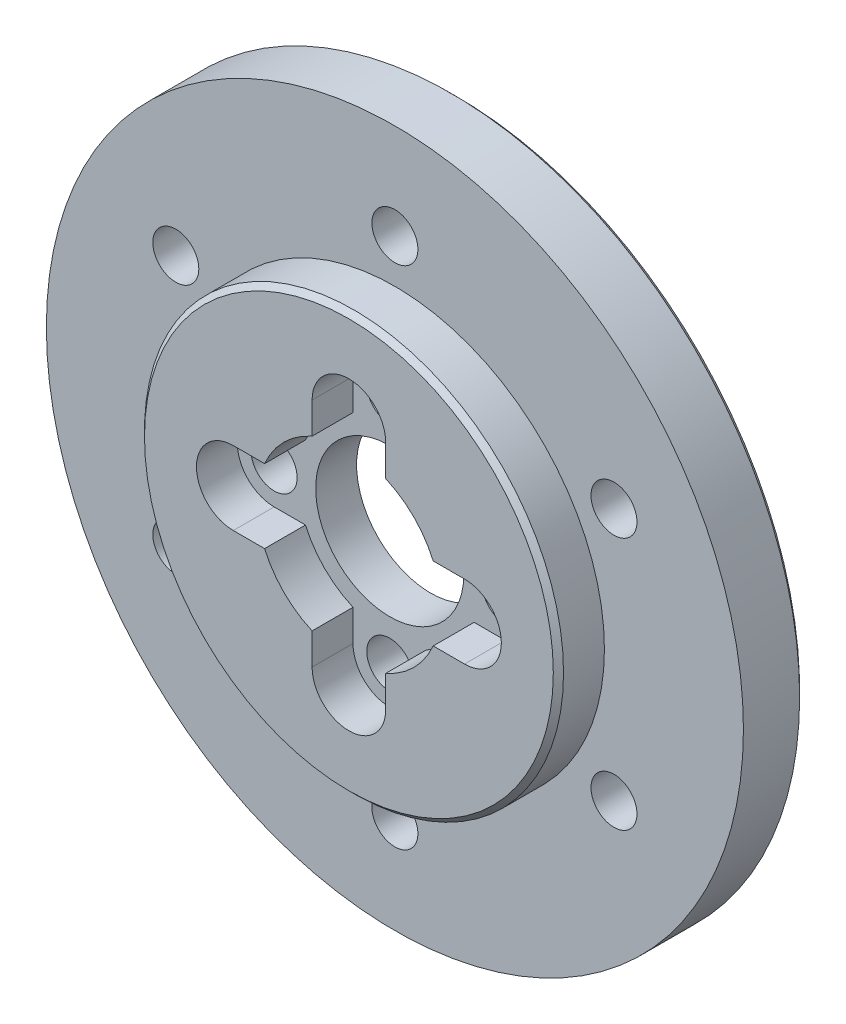
SolidWorks part; units mm, degrees
material "6061-T6 (SS)"
ref_plane "Front Plane" through (0, 0, 0) normal (0, 0, 1) x (1, 0, 0)
ref_plane "Top Plane" through (0, 0, 0) normal (0, 1, 0) x (1, 0, 0)
ref_plane "Right Plane" through (0, 0, 0) normal (1, 0, 0) x (0, 0, -1)
sketch "Sketch1" plane through (0, 0, 0) normal (0, 0, 1) x (1, 0, 0)
  circle A0 centre (0, 0) radius 34.1
  dimension "D1" = 68.2
extrude "Boss-Extrude1" add sketch "Sketch1" along normal mid plane 3.5
sketch "Sketch4" plane through (0, 0, 1.75) normal (0, 0, 1) x (1, 0, 0)
  circle A0 centre (0, 0) radius 28.5
  dimension "D1" = 57
extrude "Boss-Extrude2" add sketch "Sketch4" along normal blind 2
sketch "Sketch5" plane through (0, 0, -1.75) normal (0, 0, -1) x (-1, 0, 0)
  circle A0 centre (0, 0) radius 16.25
  circle A1 centre (0, 0) radius 34.1 construction
  circle A2 centre (0, 0) radius 34.1
  dimension "D1" = 32.5
extrude "Boss-Extrude3" add sketch "Sketch5" along normal blind 2.5
sketch "Sketch3" plane through (0, 0, 1.75) normal (0, 0, 1) x (1, 0, 0)
  circle A8 centre (0, 0) radius 11.3137 construction
  circle A9 centre (0, 11.3137) radius 2.25
  circle A11 centre (11.3137, 0) radius 2.25
  circle A13 centre (0, -11.3137) radius 2.25
  circle A15 centre (-11.3137, 0) radius 2.25
  point P21 (0, 0)
  dimension "D3" = 22.6274
  dimension "D4" = 4.5
  dimension "D5" = 4
extrude "Cut-Extrude2" cut sketch "Sketch3" against normal through all both and the other way through all
sketch "Sketch2" plane through (0, 0, 1.75) normal (0, 0, 1) x (1, 0, 0)
  circle A0 centre (0, 0) radius 7.25
  dimension "D1" = 14.5
extrude "Cut-Extrude1" cut sketch "Sketch2" along normal through all both and the other way through all
sketch "Sketch7" plane through (0, 0, 3.75) normal (0, 0, 1) x (1, 0, 0)
  circle A0 centre (0, 0) radius 20.5
  circle A5 centre (0, -11.3137) radius 2.25 construction
  circle A6 centre (11.3137, 0) radius 2.25 construction
  circle A7 centre (0, 11.3137) radius 2.25 construction
  circle A8 centre (-11.3137, 0) radius 2.25 construction
  circle A9 centre (0, 0) radius 7.25 construction
  circle A10 centre (0, -11.3137) radius 2.25
  circle A11 centre (11.3137, 0) radius 2.25
  circle A12 centre (0, 11.3137) radius 2.25
  circle A13 centre (-11.3137, 0) radius 2.25
  circle A14 centre (0, 0) radius 7.25
  dimension "D1" = 41
extrude "Boss-Extrude4" add sketch "Sketch7" along normal blind 2.5
sketch "Sketch8" plane through (0, 0, 1.75) normal (0, 0, 1) x (1, 0, 0)
  circle A0 centre (0, 0) radius 28.5 construction
  circle A1 centre (0, 0) radius 34.1
  circle A2 centre (0, 0) radius 34.1
  circle A3 centre (0, 0) radius 28.5
  dimension "D1" = 0
extrude "Boss-Extrude5" add sketch "Sketch8" along normal up to surface (2 mm away) up to face at (20.5, 0, 3.75)
sketch "Sketch10" plane through (0, 0, 3.75) normal (0, 0, 1) x (1, 0, 0)
  circle A0 centre (0, 0) radius 20.5 construction
  circle A1 centre (0, 0) radius 34.1
  circle A2 centre (0, 0) radius 34.1
  circle A3 centre (0, 0) radius 20.5
  dimension "D1" = 0
extrude "Cut-Extrude4" cut sketch "Sketch10" against normal blind 2
sketch "Sketch11" plane through (0, 0, 6.25) normal (0, 0, 1) x (1, 0, 0)
  line L0 (-11.3137, 3.6) -> (-8.2486, 3.6)
  line L1 (-3.6, 8.2486) -> (-3.6, 11.3137)
  line L2 (3.6, 11.3137) -> (3.6, 8.2486)
  line L3 (8.2486, 3.6) -> (11.3137, 3.6)
  line L4 (11.3137, -3.6) -> (8.2486, -3.6)
  line L5 (3.6, -8.2486) -> (3.6, -11.3137)
  line L6 (-3.6, -11.3137) -> (-3.6, -8.2486)
  line L7 (-8.2486, -3.6) -> (-11.3137, -3.6)
  circle A0 centre (-11.3137, 0) radius 2.25 construction
  circle A1 centre (0, -11.3137) radius 2.25 construction
  circle A2 centre (11.3137, 0) radius 2.25 construction
  circle A3 centre (0, 11.3137) radius 2.25 construction
  circle A4 centre (-11.3137, 0) radius 2.25 construction
  circle A5 centre (0, -11.3137) radius 2.25 construction
  circle A6 centre (11.3137, 0) radius 2.25 construction
  circle A7 centre (0, 11.3137) radius 2.25 construction
  arc A8 (-3.6, -11.3137) -> (3.6, -11.3137) centre (0, -11.3137) ccw
  arc A9 (11.3137, -3.6) -> (11.3137, 3.6) centre (11.3137, 0) ccw
  arc A10 (3.6, 11.3137) -> (-3.6, 11.3137) centre (0, 11.3137) ccw
  arc A11 (-11.3137, 3.6) -> (-11.3137, -3.6) centre (-11.3137, 0) ccw
  arc A12 (-8.2486, -3.6) -> (-3.6, -8.2486) centre (0, 0) ccw
  arc A13 (-3.6, 8.2486) -> (-8.2486, 3.6) centre (0, 0) ccw
  arc A14 (8.2486, 3.6) -> (3.6, 8.2486) centre (0, 0) ccw
  arc A15 (3.6, -8.2486) -> (8.2486, -3.6) centre (0, 0) ccw
  dimension "D1" = 7.2
  dimension "D2" = 18
extrude "Cut-Extrude5" cut sketch "Sketch11" against normal blind 4
sketch "Sketch6" plane through (0, 0, -4.25) normal (0, 0, 1) x (1, 0, 0)
  circle A0 centre (0, 24.75) radius 2.25
  dimension "D1" = 4.5
  dimension "D2" = 24.75
extrude "Cut-Extrude3" cut sketch "Sketch6" against normal through all both and the other way through all
sketch "Sketch12" plane through (0, 0, -4.25) normal (0, 0, -1) x (-1, 0, 0)
  circle A0 centre (0, 24.75) radius 2.25 construction
  circle A1 centre (0, 24.75) radius 2.25 construction
  circle A2 centre (0, 24.75) radius 3.75
  dimension "D1" = 7.5
extrude "Cut-Extrude6" cut sketch "Sketch12" against normal blind 2
pattern_circular "CirPattern1" count 6 over 360 about axis through (0, 0, 1.75) along (0, 0, -1) of "Cut-Extrude3", "Cut-Extrude6"
chamfer "Chamfer1" distance 0.5 angle 45 2 edges at (-34.1, 0, -4.25) (20.5, 0, 6.25)
